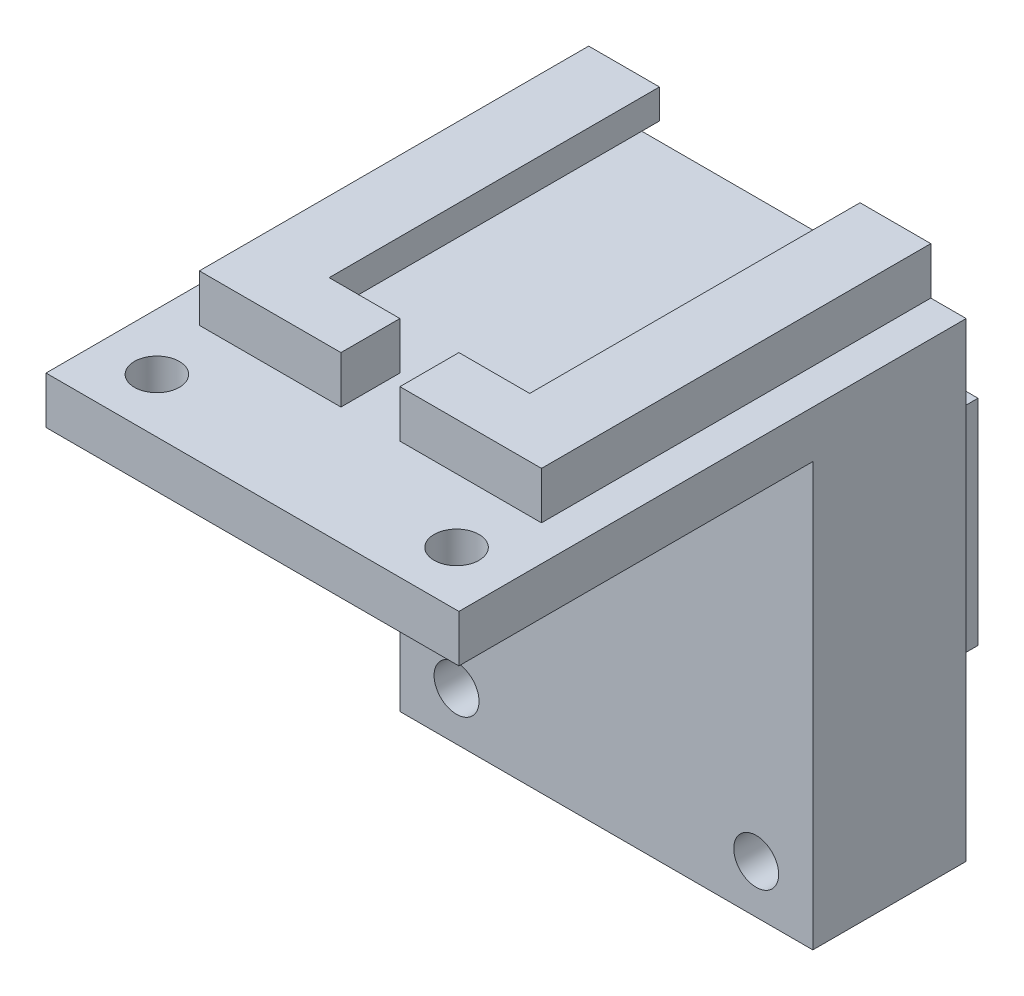
SolidWorks part; units mm, degrees
ref_plane "Front Plane" through (0, 0, 0) normal (0, 0, 1) x (1, 0, 0)
ref_plane "Top Plane" through (0, 0, 0) normal (0, 1, 0) x (1, 0, 0)
ref_plane "Right Plane" through (0, 0, 0) normal (1, 0, 0) x (0, 0, -1)
sketch "Sketch1" plane through (0, 0, 0) normal (0, 1, 0) x (1, 0, 0)
  line L1 (0, 0) -> (29, 0)
  line L2 (0, 0) -> (0, 15)
  line L3 (0, 15) -> (29, 15)
  line L4 (29, 0) -> (29, 15)
  dimension "D1" = 29
  dimension "D2" = 15
extrude "Boss-Extrude1" add sketch "Sketch1" along normal blind 8
sketch "Sketch2" plane through (0, 0, 0) normal (0, 0, 1) x (1, 0, 0)
  line L0 (0, 0) -> (29, 0) construction
  line L1 (4, 5.5) -> (25, 5.5)
  line L2 (4, 5.5) -> (4, 3.5)
  line L3 (4, 3.5) -> (25, 3.5)
  line L4 (25, 5.5) -> (25, 3.5)
  line L5 (0, 8) -> (29, 8) construction
  line L6 (6, 8) -> (23, 8)
  line L7 (6, 8) -> (6, 5.5)
  line L8 (6, 5.5) -> (23, 5.5)
  line L9 (23, 8) -> (23, 5.5)
  line L10 (0, 8) -> (0, 0) construction
  point P12 (14.5, 0)
  point P13 (14.5, 3.5)
  point P14 (14.5, 8)
  line M11 (29, 8) -> (0, 8)
  dimension "D1" = 3.5
  dimension "D2" = 2
  dimension "D3" = 6
  dimension "D4" = 4
extrude "Cut-Extrude1" cut sketch "Sketch2" against normal through all both and the other way through all contours L9 L7 L1 M11 | L4 L1 L2 L3 region at (14.5, 4.5, 0) region at (14.5, 6.75, 0)
sketch "Sketch4" plane through (0, 0, 0) normal (0, 0, 1) x (1, 0, 0)
  line L1 (0, 8) -> (29, 8)
  line L2 (0, 8) -> (0, 0)
  line L3 (0, 0) -> (29, 0)
  line L4 (29, 8) -> (29, 0)
  line L5 (12, 8) -> (17, 8)
  line L6 (12, 8) -> (12, 0)
  line L7 (12, 0) -> (17, 0)
  line L8 (17, 8) -> (17, 0)
  point P10 (14.5, 8)
  point P11 (14.5, 8)
  line M1 (23, 8) -> (23, 5.5)
  line M2 (23, 5.5) -> (25, 5.5)
  line M3 (25, 5.5) -> (25, 3.5)
  line M4 (25, 3.5) -> (4, 3.5)
  line M5 (4, 3.5) -> (4, 5.5)
  line M6 (4, 5.5) -> (6, 5.5)
  line M7 (6, 5.5) -> (6, 8)
  line M8 (6, 8) -> (0, 8)
  line M9 (0, 8) -> (0, 0)
  line M10 (0, 0) -> (29, 0)
  line M11 (29, 0) -> (29, 8)
  line M12 (29, 8) -> (23, 8)
  dimension "D1" = 5
extrude "Boss-Extrude2" add sketch "Sketch4" along normal blind 5 contours L8 L6 L3 M4 | L8 M4 M10 M11 M12 M1 M2 M3 | L6 M4 M5 M6 M7 M8 M9 M10 | L6 L1 M7 M6 M5 M4 | L1 L8 M4 M3 M2 M1 region at (4.8154, 3.2423, 0) region at (8.4839, 5.5887, 0) region at (14.5, 1.75, 0) region at (20.5161, 5.5887, 0) region at (24.1846, 3.2423, 0)
sketch "Sketch5" plane through (0, 0, 0) normal (0, -1, 0) x (-1, 0, 0)
  line L0 (-29, 15) -> (0, 15) construction
  line L1 (3, 15) -> (-32, 15)
  line L2 (3, 15) -> (3, -15)
  line L3 (3, -15) -> (-32, -15)
  line L4 (-32, 15) -> (-32, -15)
  line L5 (0, -5) -> (-29, -5) construction
  point P8 (-14.5, -5)
  point P9 (-14.5, -15)
  dimension "D1" = 35
  dimension "D2" = 30
extrude "Boss-Extrude3" add sketch "Sketch5" against normal blind 4
sketch "Sketch6" plane through (0, 0, 0) normal (0, -1, 0) x (-1, 0, 0)
  line L0 (-32, -15) -> (3, -15) construction
  line L1 (-1.8, -10.4) -> (-27.2, -10.4) construction
  line L2 (-1.8, -10.4) -> (-1.8, 2.3) construction
  line L3 (-1.8, 2.3) -> (-27.2, 2.3) construction
  line L4 (-27.2, -10.4) -> (-27.2, 2.3) construction
  line L5 (-32, 15) -> (3, 15) construction
  circle A0 centre (-1.8, 2.3) radius 1.905
  circle A1 centre (-27.2, -10.4) radius 1.905
  circle A2 centre (-1.8, -10.4) radius 1.905
  circle A3 centre (-27.2, 2.3) radius 1.905
  point P16 (-14.5, -15)
  point P17 (-14.5, -10.4)
  dimension "D2" = 3.81
  dimension "D1" = 25.4
  dimension "D3" = 12.7
  dimension "D4" = 12.7
extrude "Cut-Extrude2" cut sketch "Sketch6" against normal through all both contours A1 | A2
sketch "Sketch9" plane through (0, 0, -15) normal (0, 0, -1) x (-1, 0, 0)
  line L1 (-32, 4) -> (3, 4)
  line L2 (-32, 4) -> (-32, -35.85)
  line L3 (-32, -35.85) -> (3, -35.85)
  line L4 (3, 4) -> (3, -35.85)
  dimension "D1" = 39.85
  dimension "D2" = 35
extrude "Boss-Extrude4" add sketch "Sketch9" along normal blind 13
sketch "Sketch10" plane through (0, 0, -15) normal (0, 0, 1) x (1, 0, 0)
  line L1 (32, -35.85) -> (-3, -35.85) construction
  line L2 (1.8, -19.05) -> (27.2, -19.05) construction
  line L3 (1.8, -19.05) -> (1.8, -31.75) construction
  line L4 (1.8, -31.75) -> (27.2, -31.75) construction
  line L5 (27.2, -19.05) -> (27.2, -31.75) construction
  line L6 (32, 0) -> (-3, 0) construction
  circle A0 centre (1.8, -19.05) radius 1.905
  circle A1 centre (27.2, -19.05) radius 1.905
  circle A2 centre (1.8, -31.75) radius 1.905
  circle A3 centre (27.2, -31.75) radius 1.905
  point P13 (14.5, -35.85)
  point P14 (14.5, -31.75)
  dimension "D1" = 3.81
  dimension "D2" = 19.05
  dimension "D3" = 12.7
  dimension "D4" = 25.4
extrude "Cut-Extrude4" cut sketch "Sketch10" against normal up to surface (13 mm away) contours A3 | A2 up to face at (14.5, -15.925, -28)
sketch "Sketch11" plane through (0, 0, -28) normal (0, 0, -1) x (-1, 0, 0)
  line L0 (3, 4) -> (-32, 4) construction
  line L1 (0, -5.35) -> (-29, -5.35)
  line L2 (0, -5.35) -> (0, -18.5)
  line L3 (0, -18.5) -> (-29, -18.5)
  line L4 (-29, -5.35) -> (-29, -18.5)
  line L5 (-32, -35.85) -> (3, -35.85) construction
  point P6 (-14.5, -35.85)
  point P9 (-14.5, -18.5)
  dimension "D1" = 22.5
  dimension "D2" = 9.35
  dimension "D3" = 29
extrude "Boss-Extrude5" add sketch "Sketch11" along normal blind 4
sketch "Sketch12" plane through (0, -5.35, 0) normal (0, 1, 0) x (1, 0, 0)
  line L0 (0, 28) -> (29, 28) construction
  line L1 (4, 28) -> (25, 28)
  line L2 (4, 28) -> (4, 29.5)
  line L3 (4, 29.5) -> (25, 29.5)
  line L4 (25, 28) -> (25, 29.5)
  line L5 (6, 29.5) -> (23, 29.5)
  line L6 (6, 29.5) -> (6, 32)
  line L7 (6, 32) -> (23, 32)
  line L8 (23, 29.5) -> (23, 32)
  line L9 (0, 32) -> (29, 32) construction
  line L10 (29, 32) -> (29, 28) construction
  point P10 (14.5, 28)
  point P11 (14.5, 28)
  point P12 (14.5, 29.5)
  line M9 (0, 28) -> (29, 28)
  line M11 (29, 32) -> (0, 32)
  dimension "D1" = 1.5
  dimension "D2" = 6
  dimension "D3" = 4
extrude "Cut-Extrude5" cut sketch "Sketch12" along direction (0, 1, 0) on the side against the normal through all contours L4 L3 L2 M9 | L3 L8 L6 M11 region at (14.5, -5.35, -28.75) region at (14.5, -5.35, -30.75)
sketch "Sketch13" plane through (0, -18.5, 0) normal (0, -1, 0) x (-1, 0, 0)
  line L0 (0, 32) -> (0, 28) construction
  line L1 (0, 28) -> (-29, 28)
  line L2 (0, 28) -> (0, 32)
  line L3 (0, 32) -> (-29, 32)
  line L4 (-29, 28) -> (-29, 32)
  line L5 (-12, 32) -> (-17, 32)
  line L6 (-12, 32) -> (-12, 28)
  line L7 (-12, 28) -> (-17, 28)
  line L8 (-17, 32) -> (-17, 28)
  line L10 (-4, 28) -> (0, 28) construction
  point P11 (-14.5, 28)
  point P12 (-14.5, 28)
  line M1 (-4, 29.5) -> (-4, 28)
  line M2 (-4, 28) -> (0, 28)
  line M3 (0, 28) -> (0, 32)
  line M4 (0, 32) -> (-6, 32)
  line M5 (-6, 32) -> (-6, 29.5)
  line M6 (-6, 29.5) -> (-4, 29.5)
  dimension "D1" = 5
extrude "Boss-Extrude6" add sketch "Sketch13" along normal blind 5 contours M6 M1 M2 M3 M4 M5 | L6 L1 M6 M1 | L8 L3 L4 L1 region at (2.7143, -18.5, -30.1786) region at (8.5556, -18.5, -29.8611) region at (23, -18.5, -30)
sketch "Sketch14" plane through (0, 0, -15) normal (0, 0, -1) x (-1, 0, 0)
  line L0 (-6, 8) -> (-6, 5.5) construction
  line L1 (0, 8) -> (-29, 8)
  line L2 (0, 8) -> (0, 4)
  line L3 (0, 4) -> (-29, 4)
  line L4 (-29, 8) -> (-29, 4)
  line L5 (-4, 4) -> (-25, 4)
  line L6 (-4, 4) -> (-4, 5.5)
  line L7 (-4, 5.5) -> (-25, 5.5)
  line L8 (-25, 4) -> (-25, 5.5)
  line L9 (-23, 8) -> (-6, 8)
  line L10 (-23, 8) -> (-23, 5.5)
  line L11 (-23, 5.5) -> (-6, 5.5)
  line L12 (-6, 8) -> (-6, 5.5)
  line M5 (-4, 4) -> (0, 4)
  line M6 (0, 4) -> (0, 8)
  line M7 (0, 8) -> (-6, 8)
  line M8 (-6, 8) -> (-6, 5.5)
  line M9 (-6, 5.5) -> (-4, 5.5)
  line M10 (-4, 5.5) -> (-4, 4)
extrude "Boss-Extrude7" add sketch "Sketch14" along normal up to surface (13 mm away) contours M10 M5 M6 M7 M8 M9 | L10 L1 L4 L3 L8 L7 region at (2.7143, 6.1786, -15) region at (26.2857, 6.1786, -15) up to face at (23.6667, -15.7833, -28)
